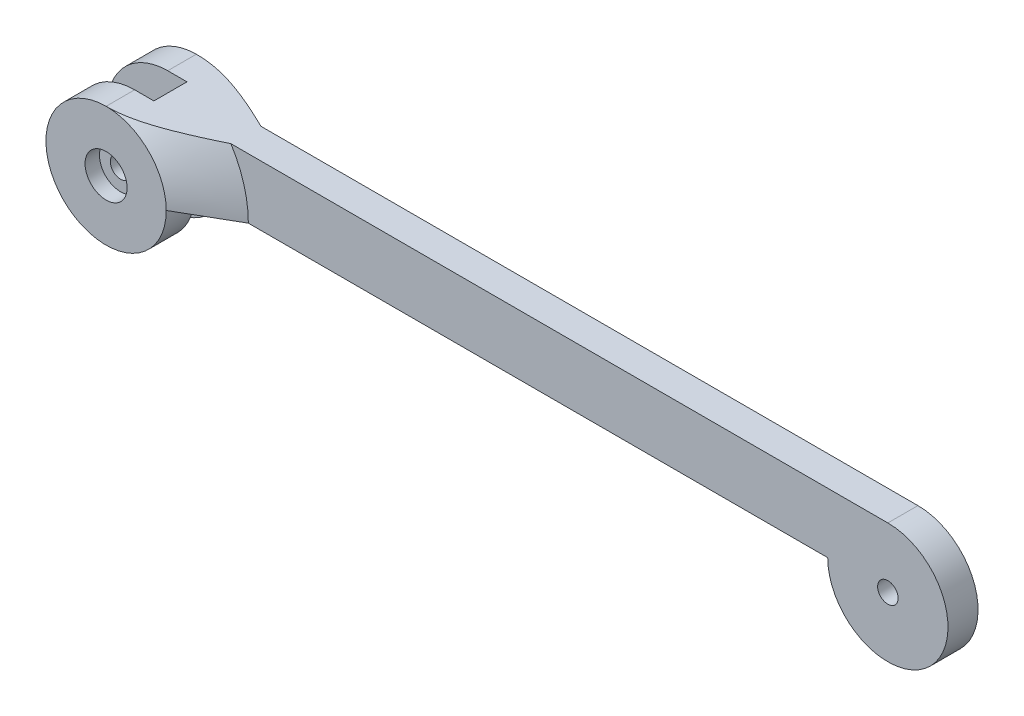
SolidWorks part; units mm, degrees
ref_plane "Front Plane" through (0, 0, 0) normal (0, 0, 1) x (1, 0, 0)
ref_plane "Top Plane" through (0, 0, 0) normal (0, 1, 0) x (1, 0, 0)
ref_plane "Right Plane" through (0, 0, 0) normal (1, 0, 0) x (0, 0, -1)
sketch "Sketch1" plane through (0, 0, 0) normal (0, 0, 1) x (1, 0, 0)
  line L0 (10, 0) -> (115, 0)
  line L1 (125, 10) -> (0, 10)
  line L2 (10, 0) -> (10, 11.407) construction
  line L3 (115, 0) -> (115, 21.6125) construction
  arc A0 (0, 10) -> (10, 0) centre (0, 0) ccw
  arc A1 (125, 10) -> (115, 0) centre (125, 0) cw
  dimension "D1" = 10
  dimension "D3" = 90
  dimension "D5" = 10
  dimension "D2" = 125
  dimension "D4" = 90
extrude "Boss-Extrude1" add sketch "Sketch1" along normal mid plane 5
sketch "Sketch8" plane through (0, 0, 0) normal (0, 0, 1) x (1, 0, 0)
  circle A0 centre (0, 0) radius 10
extrude "Boss-Extrude3" add sketch "Sketch8" along normal mid plane 15
chamfer "Chamfer1" distance 5 angle 60 2 edges at (7.0711, 7.0711, -2.5) (7.0711, 7.0711, 2.5) first distance on face at (6.0355, 6.0355, 0)
sketch "Sketch9" plane through (0, 0, 0) normal (0, 0, 1) x (1, 0, 0)
  circle A0 centre (0, 0) radius 10.5
  dimension "D1" = 21
extrude "Cut-Extrude4" cut sketch "Sketch9" against normal mid plane 5.5
hole_wizard "CBORE for M3 Pan Head Screw1" positions "Sketch11" profile "Sketch12" counterbore size "M3" standard "ISO" end condition through all
sketch "Sketch11" plane through (0, 0, 7.5) normal (0, 0, 1) x (1, 0, 0)
  point P0 (0, 0)
sketch "Sketch12" plane through (0, 0, 7.5) normal (1, 0, 0) x (0, -1, 0)
  line L0 (0, 0) -> (0, 15)
  line L1 (0, 15) -> (1.7, 15)
  line L3 (1.7, 15) -> (1.7, 2.4)
  line L4 (1.7, 2.4) -> (3.5, 2.4)
  line L5 (3.5, 2.4) -> (3.5, 0)
  line L7 (3.5, 0) -> (0, 0)
  line L11 (0, -6.35) -> (0, 107.95) construction
  dimension "Thru Hole Dia." = 3.4
  dimension "Thru Hole Depth" = 15
  dimension "C'Bore Dia." = 7
  dimension "C'Bore Depth" = 2.4
sketch "Sketch13" plane through (0, 0, -7.5) normal (0, 0, -1) x (-1, 0, 0)
  line L1 (1.6166, 2.8) -> (-1.6166, 2.8)
  line L2 (-1.6166, 2.8) -> (-3.2332, 0)
  line L3 (-3.2332, 0) -> (-1.6166, -2.8)
  line L4 (-1.6166, -2.8) -> (1.6166, -2.8)
  line L5 (1.6166, -2.8) -> (3.2332, 0)
  line L6 (3.2332, 0) -> (1.6166, 2.8)
  circle A0 centre (0, 0) radius 2.8 construction
  dimension "D1" = 5.6
extrude "Cut-Extrude5" cut sketch "Sketch13" against normal blind 3
hole_wizard "M3 Clearance Hole1" positions "Sketch15" profile "Sketch16" hole size "M3" standard "ISO"
sketch "Sketch15" plane through (0, 0, 2.5) normal (0, 0, 1) x (1, 0, 0)
  point P0 (125, 0)
sketch "Sketch16" plane through (125, 0, 2.5) normal (1, 0, 0) x (0, -1, 0)
  line L0 (0, 0) -> (0, 6.0215)
  line L1 (0, 6.0215) -> (1.7, 5)
  line L2 (1.7, 5) -> (1.7, 0)
  line L5 (1.7, 0) -> (0, 0)
  line L10 (0, 6.0215) -> (-1.7, 5) construction
  line L11 (0, -6.35) -> (0, 107.95) construction
  dimension "Hole Dia." = 3.4
  dimension "Hole Depth" = 5
  dimension "Drill Angle" = 118
